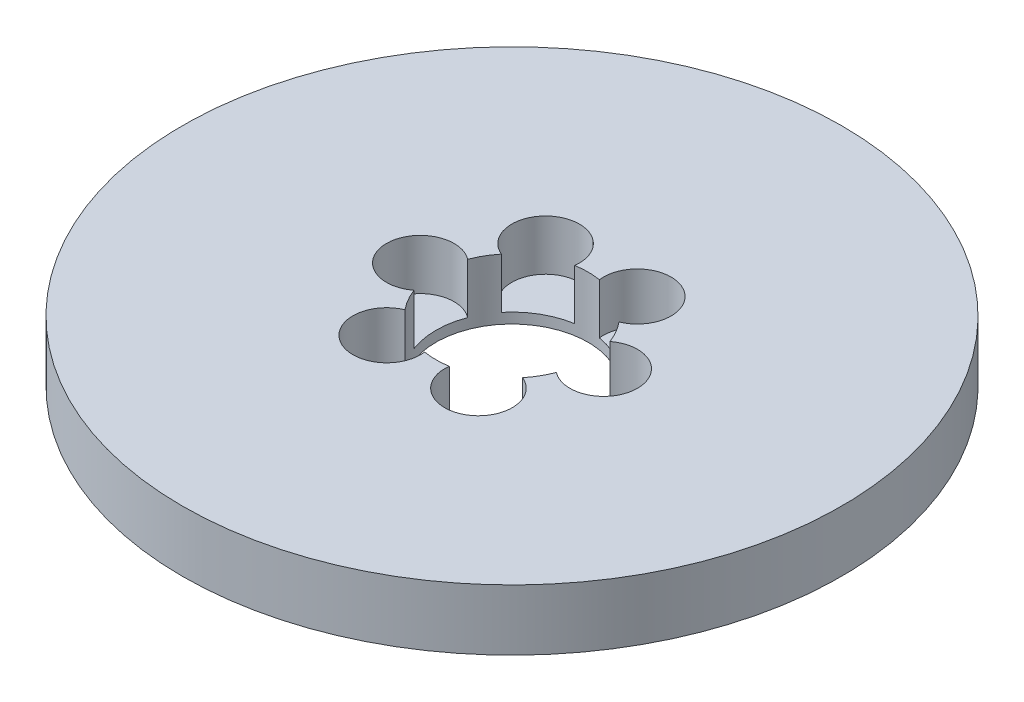
SolidWorks part; units mm, degrees
ref_plane "Front Plane" through (0, 0, 0) normal (0, 0, 1) x (1, 0, 0)
ref_plane "Top Plane" through (0, 0, 0) normal (0, 1, 0) x (1, 0, 0)
ref_plane "Right Plane" through (0, 0, 0) normal (1, 0, 0) x (0, 0, -1)
sketch "Sketch1" plane through (0, 0, 0) normal (0, 1, 0) x (1, 0, 0)
  circle A0 centre (0, 0) radius 97.5
  dimension "FLANGE_OD" = 195
extrude "Boss-Extrude1" add sketch "Sketch1" along normal blind 18
sketch "Sketch2" plane through (0, 0, 0) normal (0, 1, 0) x (1, 0, 0)
  circle A0 centre (0, 0) radius 22.5
  dimension "BORE_D" = 45
extrude "Cut-Extrude1" cut sketch "Sketch2" along normal through all
sketch "Sketch3" plane through (0, 18, 0) normal (0, 1, 0) x (1, 0, 0)
  circle A0 centre (0, 0) radius 27.1311 construction
  circle A1 centre (-27.1311, 0) radius 10
  dimension "BOLT_D" = 20
  dimension "BOLT_PCD" = 54.2622
extrude "Cut-Extrude2" cut sketch "Sketch3" against normal blind 14.9287
pattern_circular "CirPattern1" count 6 over 360 about axis through (0, 0, 0) along (0, 1, 0) of "Cut-Extrude2"
